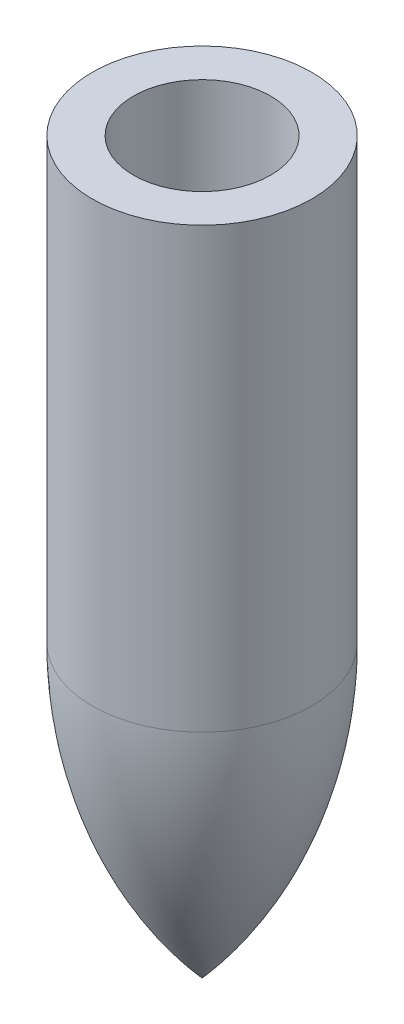
SolidWorks part; units mm, degrees
ref_plane "Front" through (0, 0, 0) normal (0, 0, 1) x (1, 0, 0)
ref_plane "Top" through (0, 0, 0) normal (0, 1, 0) x (1, 0, 0)
ref_plane "Right" through (0, 0, 0) normal (1, 0, 0) x (0, 0, -1)
ref_axis "Center Axis" through (0, 0, -13.97) along (0, 0, 1)
sketch "Sketch1" plane through (0, 0, 0) normal (0, 0, 1) x (1, 0, 0)
  line L0 (0, 0) -> (0, -50.8)
  line L1 (12.7, -84.401) -> (12.7, 0)
  line L2 (12.7, 0) -> (0, 0)
  arc A0 (0, -50.8) -> (12.7, -84.401) centre (50.8, -50.8) ccw
  dimension "D4" = 50.8
  dimension "D1" = 12.7
  dimension "D3" = 50.8
revolve "Revolve1" add sketch "Sketch1" angle 360 about L1
shell "Shell2" thickness 4.7625 removed face at (25.4, 0, 0)
